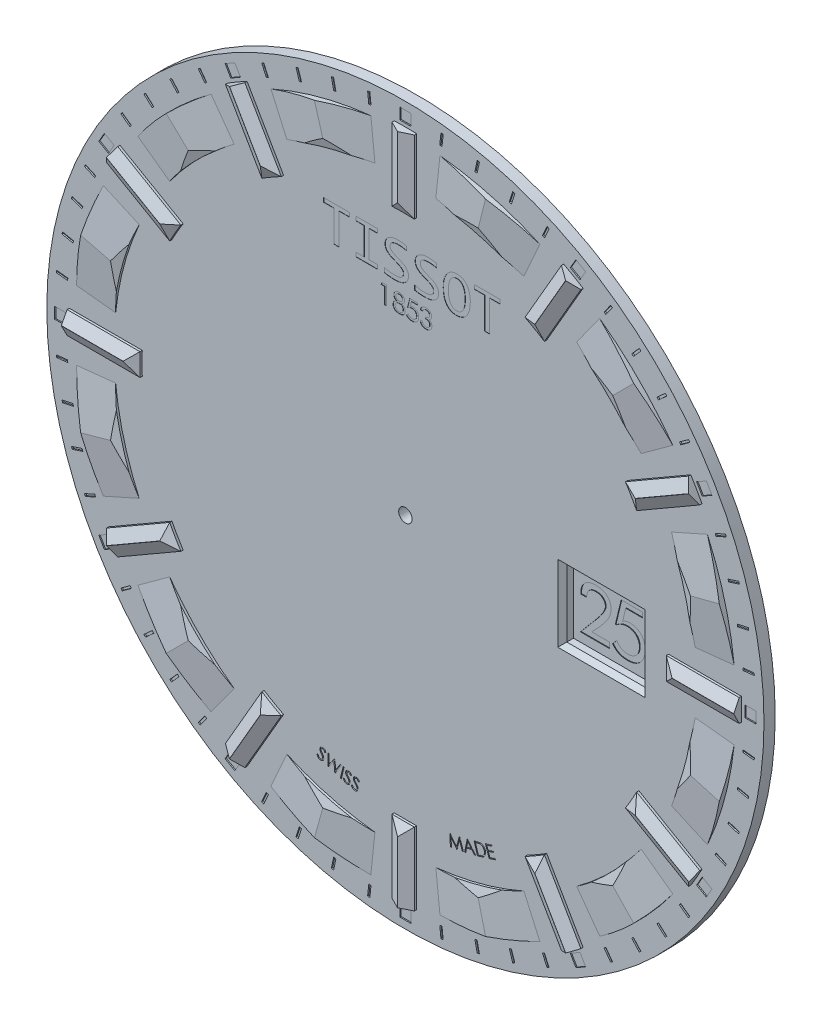
SolidWorks part; units mm, degrees
ref_plane "Front Plane" through (0, 0, 0) normal (0, 0, 1) x (1, 0, 0)
ref_plane "Top Plane" through (0, 0, 0) normal (0, 1, 0) x (1, 0, 0)
ref_plane "Right Plane" through (0, 0, 0) normal (1, 0, 0) x (0, 0, -1)
sketch "Sketch1" plane through (0, 0, 0) normal (0, 0, 1) x (1, 0, 0)
  circle A0 centre (0, 0) radius 16
  dimension "D1" = 32
extrude "Boss-Extrude1" add sketch "Sketch1" along normal blind 0.5
sketch "Sketch2" plane through (0, 0, 0.5) normal (0, 0, 1) x (1, 0, 0)
  circle A0 centre (0, 0) radius 14.5
  circle A1 centre (0, 0) radius 13
  circle A2 centre (0, 0) radius 15
  circle A3 centre (0, 0) radius 11.75
  dimension "D1" = 30
  dimension "D2" = 23.5
  dimension "D3" = 26
  dimension "D4" = 29
sketch "Sketch3" plane through (0, 0, 0.5) normal (0, 0, 1) x (1, 0, 0)
  line L0 (0.5, -14.9917) -> (0.5, -11.75)
  line L2 (-0.5, -14.9917) -> (-0.5, -11.75)
  line L3 (-0.5, -11.75) -> (0.5, -11.75)
  line L4 (-0.5, -14.9917) -> (0.5, -14.9917)
  line L13 (0.5, 14.9917) -> (0.5, 11.7394)
  line L14 (-7.0628, 13.2332) -> (-5.4367, 10.4166)
  line L15 (-12.7332, 7.9288) -> (-9.9166, 6.3027)
  line L16 (-14.9917, 0.5) -> (-11.7394, 0.5)
  line L17 (-13.2332, -7.0628) -> (-10.4166, -5.4367)
  line L18 (7.9288, 12.7332) -> (6.3027, 9.9166)
  line L19 (-0.5, 14.9917) -> (-0.5, 11.7394)
  line L20 (-7.9288, 12.7332) -> (-6.3027, 9.9166)
  line L21 (-13.2332, 7.0628) -> (-10.4166, 5.4367)
  line L22 (-14.9917, -0.5) -> (-11.7394, -0.5)
  line L23 (-12.7332, -7.9288) -> (-9.9166, -6.3027)
  line L24 (7.0628, 13.2332) -> (5.4367, 10.4166)
  line L25 (12.7332, 7.9288) -> (9.9166, 6.3027)
  line L26 (13.2332, 7.0628) -> (10.4166, 5.4367)
  line L27 (14.9917, 0.5) -> (11.7394, 0.5)
  line L28 (13.2332, -7.0628) -> (10.4166, -5.4367)
  line L29 (7.9288, -12.7332) -> (6.3027, -9.9166)
  line L30 (-7.0628, -13.2332) -> (-5.4367, -10.4166)
  line L31 (14.9917, -0.5) -> (11.7394, -0.5)
  line L32 (12.7332, -7.9288) -> (9.9166, -6.3027)
  line L33 (7.0628, -13.2332) -> (5.4367, -10.4166)
  line L34 (-7.9288, -12.7332) -> (-6.3027, -9.9166)
  arc A0 (-12.7332, 7.9288) -> (-13.2332, 7.0628) centre (0, 0) ccw
  arc A1 (-9.9166, 6.3027) -> (-10.4166, 5.4367) centre (0, 0) ccw
  arc A2 (-5.4367, 10.4166) -> (-6.3027, 9.9166) centre (0, 0) ccw
  arc A3 (-7.0628, 13.2332) -> (-7.9288, 12.7332) centre (0, 0) ccw
  arc A4 (0.5, 11.7394) -> (-0.5, 11.7394) centre (0, 0) ccw
  arc A5 (0.5, 14.9917) -> (-0.5, 14.9917) centre (0, 0) ccw
  arc A6 (-6.3027, -9.9166) -> (-5.4367, -10.4166) centre (0, 0) ccw
  arc A7 (-7.9288, -12.7332) -> (-7.0628, -13.2332) centre (0, 0) ccw
  arc A8 (-13.2332, -7.0628) -> (-12.7332, -7.9288) centre (0, 0) ccw
  arc A9 (-10.4166, -5.4367) -> (-9.9166, -6.3027) centre (0, 0) ccw
  arc A10 (-11.7394, 0.5) -> (-11.7394, -0.5) centre (0, 0) ccw
  arc A11 (-14.9917, 0.5) -> (-14.9917, -0.5) centre (0, 0) ccw
  arc A12 (7.9288, 12.7332) -> (7.0628, 13.2332) centre (0, 0) ccw
  arc A13 (13.2332, 7.0628) -> (12.7332, 7.9288) centre (0, 0) ccw
  arc A14 (10.4166, 5.4367) -> (9.9166, 6.3027) centre (0, 0) ccw
  arc A15 (11.7394, -0.5) -> (11.7394, 0.5) centre (0, 0) ccw
  arc A16 (14.9917, -0.5) -> (14.9917, 0.5) centre (0, 0) ccw
  arc A17 (12.7332, -7.9288) -> (13.2332, -7.0628) centre (0, 0) ccw
  arc A18 (9.9166, -6.3027) -> (10.4166, -5.4367) centre (0, 0) ccw
  arc A19 (5.4367, -10.4166) -> (6.3027, -9.9166) centre (0, 0) ccw
  arc A20 (7.0628, -13.2332) -> (7.9288, -12.7332) centre (0, 0) ccw
  arc A21 (6.3027, 9.9166) -> (5.4367, 10.4166) centre (0, 0) ccw
  circle A22 centre (0, 0) radius 15 construction
extrude "Boss-Extrude2" add sketch "Sketch3" along normal blind 0.35
chamfer "Chamfer1" distance 0.25 angle 63.3 36 edges at (13.3655, 0.5, 0.85) (13.3655, -0.5, 0.85) (11.75, 0, 0.85) (11.8249, -6.2497, 0.85) (11.3249, -7.1158, 0.85) (10.1758, -5.875, 0.85) (7.1158, -11.3249, 0.85) (6.2497, -11.8249, 0.85) (5.875, -10.1758, 0.85) (0.5, -13.3708, 0.85) (0, -11.75, 0.85) (-0.5, -13.3708, 0.85) (-6.2497, -11.8249, 0.85) (-7.1158, -11.3249, 0.85) (-5.875, -10.1758, 0.85) (-11.3249, -7.1158, 0.85) (-10.1758, -5.875, 0.85) (-11.8249, -6.2497, 0.85) (-13.3655, 0.5, 0.85) (-11.75, 0, 0.85) (-13.3655, -0.5, 0.85) (-11.3249, 7.1158, 0.85) (-11.8249, 6.2497, 0.85) (-10.1758, 5.875, 0.85) (11.8249, 6.2497, 0.85) (10.1758, 5.875, 0.85) (11.3249, 7.1158, 0.85) (6.2497, 11.8249, 0.85) (7.1158, 11.3249, 0.85) (5.875, 10.1758, 0.85) (0.5, 13.3655, 0.85) (0, 11.75, 0.85) (-0.5, 13.3655, 0.85) (-6.2497, 11.8249, 0.85) (-5.875, 10.1758, 0.85) (-7.1158, 11.3249, 0.85)
sketch "Sketch4" plane through (0, 0, 0.5) normal (0, 0, 1) x (1, 0, 0)
  line L2 (1.3589, 12.9288) -> (1.5418, 14.6692)
  line L5 (5.2876, 11.8761) -> (5.9994, 13.4748)
  line L7 (7.6412, 10.5172) -> (8.6698, 11.933)
  line L10 (10.5172, 7.6412) -> (11.933, 8.6698)
  line L12 (11.8761, 5.2876) -> (13.4748, 5.9994)
  line L15 (12.9288, 1.3589) -> (14.6692, 1.5418)
  line L17 (12.9288, -1.3589) -> (14.6692, -1.5418)
  line L20 (11.8761, -5.2876) -> (13.4748, -5.9994)
  line L22 (10.5172, -7.6412) -> (11.933, -8.6698)
  line L25 (7.6412, -10.5172) -> (8.6698, -11.933)
  line L27 (5.2876, -11.8761) -> (5.9994, -13.4748)
  line L30 (1.3589, -12.9288) -> (1.5418, -14.6692)
  line L32 (-1.3589, -12.9288) -> (-1.5418, -14.6692)
  line L35 (-5.2876, -11.8761) -> (-5.9994, -13.4748)
  line L37 (-7.6412, -10.5172) -> (-8.6698, -11.933)
  line L40 (-10.5172, -7.6412) -> (-11.933, -8.6698)
  line L42 (-11.8761, -5.2876) -> (-13.4748, -5.9994)
  line L45 (-12.9288, -1.3589) -> (-14.6692, -1.5418)
  line L47 (-12.9288, 1.3589) -> (-14.6692, 1.5418)
  line L50 (-11.8761, 5.2876) -> (-13.4748, 5.9994)
  line L52 (-10.5172, 7.6412) -> (-11.933, 8.6698)
  line L55 (-7.6412, 10.5172) -> (-8.6698, 11.933)
  line L57 (-5.2876, 11.8761) -> (-5.9994, 13.4748)
  line L60 (-1.3589, 12.9288) -> (-1.5418, 14.6692)
  line L61 (0, 0) -> (-5.2576, 16.1812) [skipped]
  line L62 (0, 0) -> (-3.5374, 16.6421) [skipped]
  line L63 (-7.375, 12.7739) -> (-8.507, 14.7345) [skipped]
  line L64 (6.5, 11.2583) -> (7.375, 12.7739) [skipped]
  line L65 (0, 0) -> (2.7029, 12.7159) [skipped]
  line L66 (0, 0) -> (4.0172, 12.3637) [skipped]
  line L67 (0, 0) -> (9.6609, 8.6987) [skipped]
  line L68 (0, 0) -> (8.6987, 9.6609) [skipped]
  line L69 (11.2583, 6.5) -> (12.7739, 7.375) [skipped]
  line L70 (13, 0) -> (17.0139, 0) [skipped]
  line L71 (12.3637, 4.0172) -> (14.0281, 4.558) [skipped]
  line L72 (12.7159, 2.7029) -> (14.4277, 3.0667) [skipped]
  line L73 (6.5, -11.2583) -> (7.375, -12.7739) [skipped]
  line L74 (11.2583, -6.5) -> (12.7739, -7.375) [skipped]
  line L75 (12.7159, -2.7029) -> (14.4277, -3.0667) [skipped]
  line L76 (12.3637, -4.0172) -> (14.0281, -4.558) [skipped]
  line L77 (9.6609, -8.6987) -> (10.9614, -9.8697) [skipped]
  line L78 (8.6987, -9.6609) -> (9.8697, -10.9614) [skipped]
  line L79 (4.0172, -12.3637) -> (4.558, -14.0281) [skipped]
  line L80 (2.7029, -12.7159) -> (3.0667, -14.4277) [skipped]
  line L81 (0, -13) -> (0, -14.75) [skipped]
  line L82 (-6.5, -11.2583) -> (-7.375, -12.7739) [skipped]
  line L83 (-4.0172, -12.3637) -> (-4.558, -14.0281) [skipped]
  line L84 (-2.7029, -12.7159) -> (-3.0667, -14.4277) [skipped]
  line L85 (-11.2583, -6.5) -> (-12.7739, -7.375) [skipped]
  line L86 (-9.6609, -8.6987) -> (-10.9614, -9.8697) [skipped]
  line L87 (-8.6987, -9.6609) -> (-9.8697, -10.9614) [skipped]
  line L88 (-13, 0) -> (-14.75, 0) [skipped]
  line L89 (-12.7159, -2.7029) -> (-14.4277, -3.0667) [skipped]
  line L90 (-12.3637, -4.0172) -> (-14.0281, -4.558) [skipped]
  line L91 (-12.7159, 2.7029) -> (-14.4277, 3.0667) [skipped]
  line L92 (-12.3637, 4.0172) -> (-14.0281, 4.558) [skipped]
  line L93 (-11.2583, 6.5) -> (-12.7739, 7.375) [skipped]
  line L94 (-9.6609, 8.6987) -> (-10.9614, 9.8697) [skipped]
  line L95 (-8.6987, 9.6609) -> (-9.8697, 10.9614) [skipped]
  line L96 (0, 13) -> (0, 17.0139) [skipped]
  arc A0 (-7.6412, 10.5172) -> (-10.5172, 7.6412) centre (0, 0) ccw
  arc A1 (-8.6698, 11.933) -> (-11.933, 8.6698) centre (0, 0) ccw
  arc A2 (5.9994, 13.4748) -> (1.5418, 14.6692) centre (0, 0) ccw
  arc A3 (5.2876, 11.8761) -> (1.3589, 12.9288) centre (0, 0) ccw
  arc A4 (11.933, 8.6698) -> (8.6698, 11.933) centre (0, 0) ccw
  arc A5 (10.5172, 7.6412) -> (7.6412, 10.5172) centre (0, 0) ccw
  arc A6 (14.6692, 1.5418) -> (13.4748, 5.9994) centre (0, 0) ccw
  arc A7 (12.9288, 1.3589) -> (11.8761, 5.2876) centre (0, 0) ccw
  arc A8 (7.6412, -10.5172) -> (10.5172, -7.6412) centre (0, 0) ccw
  arc A9 (8.6698, -11.933) -> (11.933, -8.6698) centre (0, 0) ccw
  arc A10 (11.8761, -5.2876) -> (12.9288, -1.3589) centre (0, 0) ccw
  arc A11 (13.4748, -5.9994) -> (14.6692, -1.5418) centre (0, 0) ccw
  arc A12 (1.3589, -12.9288) -> (5.2876, -11.8761) centre (0, 0) ccw
  arc A13 (1.5418, -14.6692) -> (5.9994, -13.4748) centre (0, 0) ccw
  arc A14 (-5.2876, -11.8761) -> (-1.3589, -12.9288) centre (0, 0) ccw
  arc A15 (-5.9994, -13.4748) -> (-1.5418, -14.6692) centre (0, 0) ccw
  arc A16 (-10.5172, -7.6412) -> (-7.6412, -10.5172) centre (0, 0) ccw
  arc A17 (-11.933, -8.6698) -> (-8.6698, -11.933) centre (0, 0) ccw
  arc A18 (-12.9288, -1.3589) -> (-11.8761, -5.2876) centre (0, 0) ccw
  arc A19 (-14.6692, -1.5418) -> (-13.4748, -5.9994) centre (0, 0) ccw
  arc A20 (-13.4748, 5.9994) -> (-14.6692, 1.5418) centre (0, 0) ccw
  arc A21 (-11.8761, 5.2876) -> (-12.9288, 1.3589) centre (0, 0) ccw
  arc A22 (-1.5418, 14.6692) -> (-5.9994, 13.4748) centre (0, 0) ccw
  arc A23 (-1.3589, 12.9288) -> (-5.2876, 11.8761) centre (0, 0) ccw
  dimension "D2" = 29.5
  dimension "D1" = 60
extrude "Boss-Extrude3" add sketch "Sketch4" along normal blind 0.25
chamfer "Chamfer2" distance 0.15 angle 73 12 edges at (-3.3646, -12.557, 0.75) (3.3646, -12.557, 0.75) (9.1924, -9.1924, 0.75) (12.557, -3.3646, 0.75) (12.557, 3.3646, 0.75) (9.1924, 9.1924, 0.75) (-9.1924, 9.1924, 0.75) (-3.3646, 12.557, 0.75) (3.3646, 12.557, 0.75) (-9.1924, -9.1924, 0.75) (-12.557, -3.3646, 0.75) (-12.557, 3.3646, 0.75)
sketch "Sketch5" plane through (0, 0, 0.5) normal (0, 0, 1) x (1, 0, 0)
  line L0 (0, -0.4675) -> (0, 0.4675) construction
  line L1 (7, 1.5) -> (10.5, 1.5)
  line L2 (7, 1.5) -> (7, -1.5)
  line L3 (7, -1.5) -> (10.5, -1.5)
  line L4 (10.5, 1.5) -> (10.5, -1.5)
  line L5 (0.4675, 0) -> (-0.4675, 0) construction
  dimension "D1" = 3.5
  dimension "D2" = 3
  dimension "D3" = 7
  dimension "D4" = 1.5
extrude "Cut-Extrude1" cut sketch "Sketch5" against normal blind 10.25
chamfer "Chamfer3" distance 0.2 angle 45 4 edges at (10.5, 0, 0.5) (8.75, -1.5, 0.5) (7, 0, 0.5) (8.75, 1.5, 0.5)
sketch "Sketch6" plane through (0, 0, 0.5) normal (0, 0, 1) x (1, 0, 0)
  circle A0 centre (0, 0) radius 0.3
  dimension "D1" = 0.6
extrude "Cut-Extrude2" cut sketch "Sketch6" against normal blind 10.25
sketch "Sketch7" plane through (0, 0, 0.5) normal (0, 0, 1) x (1, 0, 0)
  text T0 "1853\r\n" font "Futura Bk BT" height in points 3
extrude "Cut-Extrude3" cut sketch "Sketch7" against normal blind 0.01
sketch "Sketch9" plane through (0, 0, 0.5) normal (0, 0, 1) x (1, 0, 0)
  text T0 "TISSOT" font "Consolas" height in points 6
extrude "Cut-Extrude4" cut sketch "Sketch9" against normal blind 0.01
sketch "Sketch10" plane through (0, 0, 0) normal (0, 0, -1) x (-1, 0, 0)
  line L0 (-10.5, 1.5) -> (-7, 1.5) construction
  line L1 (-10.75, 1.75) -> (-6.75, 1.75)
  line L2 (-10.75, 1.75) -> (-10.75, -1.75)
  line L3 (-10.75, -1.75) -> (-6.75, -1.75)
  line L4 (-6.75, 1.75) -> (-6.75, -1.75)
  line L5 (-10.5, -1.5) -> (-10.5, 1.5) construction
  line L6 (-7, -1.5) -> (-10.5, -1.5) construction
  line L7 (-7, 1.5) -> (-7, -1.5) construction
  dimension "D1" = 0.25
  dimension "D2" = 0.25
  dimension "D3" = 0.25
  dimension "D4" = 0.25
extrude "Boss-Extrude4" add sketch "Sketch10" along normal blind 0.05
sketch "Sketch11" plane through (0, 0, 0) normal (0, 0, 1) x (1, 0, 0)
  text T0 "25" font "Futura Bk BT" height in points 8
extrude "Cut-Extrude5" cut sketch "Sketch11" against normal blind 0.03
sketch "Sketch13" plane through (0, 0, 0.5) normal (0, 0, 1) x (1, 0, 0)
  text T0 "  SWISS                    MADE" font "Century Gothic" height in points 2
extrude "Cut-Extrude6" cut sketch "Sketch13" against normal blind 0.05
chamfer "Chamfer4" distance 0.25 angle 84 24 edges at (14.043, 1.476, 0.75) (12.8995, 5.7432, 0.75) (14.043, -1.476, 0.75) (12.8995, -5.7432, 0.75) (8.2997, -11.4236, 0.75) (11.4236, -8.2997, 0.75) (5.7432, -12.8995, 0.75) (1.476, -14.043, 0.75) (-1.476, -14.043, 0.75) (-5.7432, -12.8995, 0.75) (-8.2997, -11.4236, 0.75) (-11.4236, -8.2997, 0.75) (-12.8995, -5.7432, 0.75) (-14.043, -1.476, 0.75) (-14.043, 1.476, 0.75) (-12.8995, 5.7432, 0.75) (-11.4236, 8.2997, 0.75) (-8.2997, 11.4236, 0.75) (11.4236, 8.2997, 0.75) (8.2997, 11.4236, 0.75) (-5.7432, 12.8995, 0.75) (-1.476, 14.043, 0.75) (5.7432, 12.8995, 0.75) (1.476, 14.043, 0.75)
sketch "Sketch14" plane through (0, 0, 0.5) normal (0, 0, 1) x (1, 0, 0)
  line L0 (0, -0.4675) -> (0, 0.4675) construction
  line L1 (-0.25, 15.65) -> (0.25, 15.65)
  line L2 (-0.25, 15.65) -> (-0.25, 15.15)
  line L3 (-0.25, 15.15) -> (0.25, 15.15)
  line L4 (0.25, 15.65) -> (0.25, 15.15)
  arc A0 (0.5, 14.9917) -> (0.0029, 15) centre (0, 0) ccw construction
  dimension "D1" = 0.5
  dimension "D2" = 0.25
  dimension "D3" = 0.5
  dimension "D4" = 15.15
extrude "Cut-Extrude7" cut sketch "Sketch14" against normal blind 0.05
pattern_circular "CirPattern1" count 12 over 360 about axis through (0, 0, 0) along (0, 0, 1) of "Cut-Extrude7"
sketch "Sketch15" plane through (0, 0, 0.5) normal (0, 0, 1) x (1, 0, 0)
  line L0 (0, 0) -> (0, 16.9206)
  line L1 (0, -0.4675) -> (0, 0.4675) construction
  line L2 (0.25, 15.65) -> (-0.25, 15.65) construction
  line L3 (-0.05, 15.65) -> (0.05, 15.65)
  line L4 (-0.05, 15.65) -> (-0.05, 15.15)
  line L5 (-0.05, 15.15) -> (0.05, 15.15)
  line L6 (0.05, 15.65) -> (0.05, 15.15)
  line L7 (-0.25, 15.15) -> (0.25, 15.15) construction
  dimension "D1" = 0.05
  dimension "D2" = 0.05
extrude "Cut-Extrude8" cut sketch "Sketch15" against normal blind 0.06 contours L6 L5 L4 L3
pattern_circular "CirPattern2" count 60 over 360 about axis through (0, 0, 0) along (0, 0, 1) skipping 5, 10, 15, 20, 25, 30, 35, 40, 45, 50, 55 of "Cut-Extrude8"
sketch "Sketch16" plane through (0, 0, 0.45) normal (0, 0, 1) x (1, 0, 0)
  line L1 (-0.25, 15.65) -> (0.25, 15.65)
  line L2 (-0.25, 15.65) -> (-0.25, 15.15)
  line L3 (-0.25, 15.15) -> (0.25, 15.15)
  line L4 (0.25, 15.65) -> (0.25, 15.15)
extrude "Boss-Extrude5" add sketch "Sketch16" against normal blind 0.01
